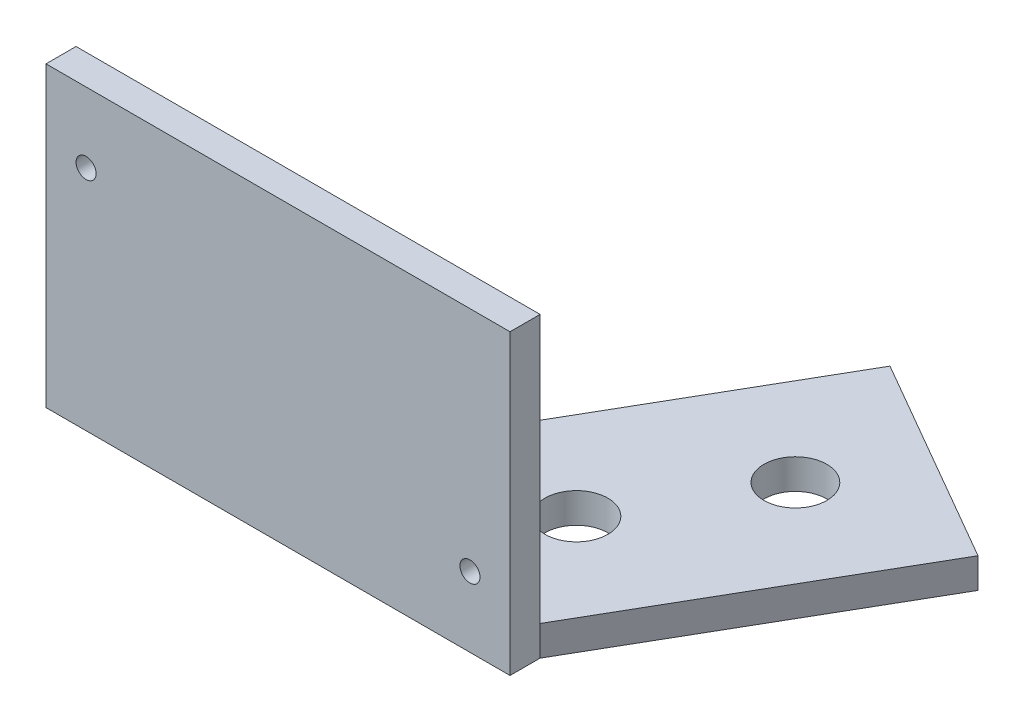
SolidWorks part; units mm, degrees
ref_plane "Front Plane" through (0, 0, 0) normal (0, 0, 1) x (1, 0, 0)
ref_plane "Top Plane" through (0, 0, 0) normal (0, 1, 0) x (1, 0, 0)
ref_plane "Right Plane" through (0, 0, 0) normal (1, 0, 0) x (0, 0, -1)
sketch "Sketch1" plane through (0, 0, 0) normal (0, 0, 1) x (1, 0, 0)
  line L1 (0, 0) -> (33.782, 0) construction
  line L2 (0, 0) -> (0, 19.812) construction
  line L3 (0, 19.812) -> (33.782, 19.812) construction
  line L4 (33.782, 0) -> (33.782, 19.812) construction
  line L5 (-1.397, -1.397) -> (35.3695, -1.397)
  line L6 (-1.397, -1.397) -> (-1.397, 19.812)
  line L7 (-1.397, 19.812) -> (35.3695, 19.812)
  line L8 (35.3695, -1.397) -> (35.3695, 19.812)
  circle A0 centre (1.778, 14.2558) radius 0.7938
  circle A1 centre (32.1945, 1.778) radius 0.7937
  dimension "D3" = 1.5875
  dimension "D4" = 1.5875
  dimension "D5" = 1.778
  dimension "D6" = 1.5875
  dimension "D7" = 1.778
  dimension "D8" = 5.5562
  dimension "D9" = 3.175
  dimension "D11" = 3.175
  dimension "D12" = 5.5562
  dimension "D1" = 19.812
  dimension "D2" = 33.782
  dimension "D10" = 3.175
extrude "Boss-Extrude1" add sketch "Sketch1" along normal blind 2.3813
sketch "Sketch2" plane through (0, -1.397, 0) normal (0, -1, 0) x (1, 0, 0)
  line L8 (-1.397, 0) -> (35.3695, 0) construction
  line L9 (-1.397, 2.3813) -> (35.3695, 2.3813)
  line L10 (-1.397, 2.3813) -> (-1.397, 0)
  line L12 (35.3695, 2.3813) -> (35.3695, 0)
  line L15 (48.0695, -21.997) -> (31.5717, -31.522)
  line L17 (48.0695, -21.997) -> (35.3695, 0)
  line L19 (31.5717, -31.522) -> (13.3725, 0)
  line L20 (13.3725, 0) -> (-1.397, 0)
  dimension "D1" = 19.05
  dimension "D2" = 25.4
  dimension "D3" = 60
extrude "Boss-Extrude3" add sketch "Sketch2" along normal blind 2.3813
sketch "Sketch4" plane through (0, -1.397, 0) normal (0, 1, 0) x (1, 0, 0)
  line L0 (39.8206, 26.7595) -> (35.801, 19.7973) construction
  line L2 (35.801, 19.7973) -> (29.451, 8.7988) construction
  line L3 (29.451, 8.7988) -> (24.371, 0) construction
  line L5 (48.0695, 21.997) -> (31.5717, 31.522) construction
  line L6 (35.3695, 0) -> (13.3725, 0) construction
  circle A0 centre (35.801, 19.7973) radius 2.4892
  circle A1 centre (29.451, 8.7988) radius 2.4892
  point P10 (24.371, 0)
  point P15 (39.8206, 26.7595)
  dimension "D1" = 4.9784
  dimension "D2" = 12.7
  dimension "D3" = 10.16
extrude "Cut-Extrude2" cut sketch "Sketch4" against normal up to next
